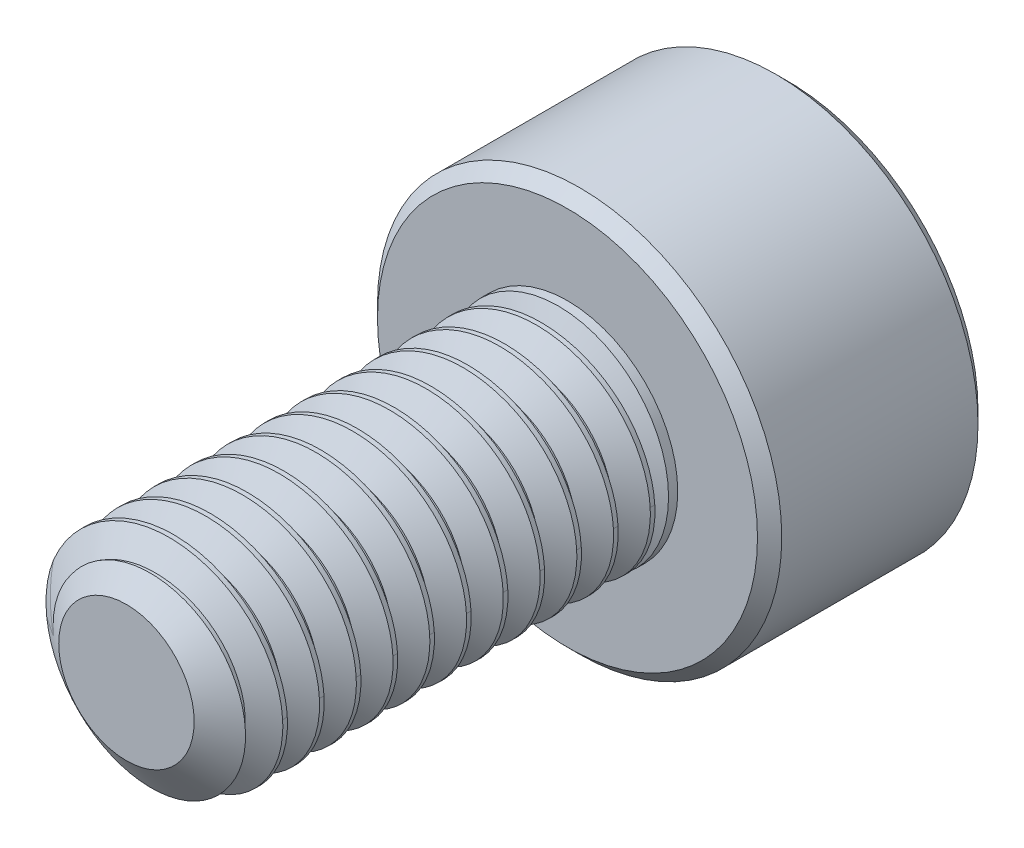
SolidWorks part; units mm, degrees
ref_plane "Front Plane" through (0, 0, 0) normal (0, 0, 1) x (1, 0, 0)
ref_plane "Top Plane" through (0, 0, 0) normal (0, 1, 0) x (1, 0, 0)
ref_plane "Right Plane" through (0, 0, 0) normal (1, 0, 0) x (0, 0, -1)
sketch "Sketch1" plane through (0, 0, 0) normal (0, 0, 1) x (1, 0, 0)
  circle A0 centre (0, 0) radius 1.5
  dimension "OD" = 3
extrude "Extrude1" add sketch "Sketch1" against normal blind 6
sketch "Sketch2" plane through (0, 0, 0) normal (0, 0, 1) x (1, 0, 0)
  circle A0 centre (0, 0) radius 1.5 construction
  circle A1 centre (0, 0) radius 1.5
curve "Helix/Spiral1" pitch 0.5 height 6.5 radius 1.5 centre (0, 0, 0) axis (0, 0, -1) start towards (0, 1, 0) parameters "pitch"=0.5
sketch "Sketch3" plane through (0, 0, 0) normal (1, 0, 0) x (0, 0, -1)
  line L0 (-0.4375, 1.5) -> (-0.25, 1.1752)
  line L1 (-0.25, 1.1752) -> (-0.1875, 1.1752)
  line L2 (-0.1875, 1.1752) -> (0, 1.5)
  line L3 (-0.4375, 1.5) -> (0, 1.5)
  line L4 (-0.2187, 1.5) -> (-0.2187, 1.1752) construction
  line L5 (-0.3437, 1.3376) -> (-0.0937, 1.3376) construction
  line L6 (0, 1.5) -> (0, -1.5) construction
  line L7 (0, -1.5) -> (6, -1.5) construction
  point P11 (2.25, -1.5)
  dimension "D1" = 0.0625
  dimension "D2" = 0.25
  dimension "D3" = 60
  dimension "D4" = 2.25
sweep "Cut-Sweep1" cut profiles "Sketch3" path "Helix/Spiral1" align with end faces yes
sketch "Sketch4" plane through (0, 0, 0) normal (1, 0, 0) x (0, 0, -1)
  line L0 (0.4053, 1.5) -> (0, 0.9212)
  line L1 (0, 0.9212) -> (0, 1.5)
  line L2 (0.4053, 1.5) -> (0, 1.5)
  line L3 (-0.4375, 1.5) -> (0, 1.5) construction
  line L4 (0, 0) -> (7.0209, 0) construction
  dimension "D1" = 55
  dimension "D2" = 0.254
revolve "Cut-Revolve1" cut sketch "Sketch4" angle 360 about L4
sketch "Sketch5" plane through (0, 0, 0) normal (1, 0, 0) x (0, 0, -1)
  line L0 (6, -1.1822) -> (6, 1.0703) construction
  line L1 (6, 1.5) -> (0.1203, 1.5)
  line L2 (6, 1.5) -> (6, 0)
  line L3 (6, 0) -> (0.0001, 0)
  line L4 (0.0001, 1.1698) -> (0.0001, 0)
  line L5 (0.1203, 1.5) -> (0.0001, 1.1698)
  line L6 (0, 0) -> (9.9695, 0) construction
  point P3 (0.0001, 1.5)
  point P10 (0.0001, 1.5)
  dimension "D1" = 0.3302
  dimension "Thread min" = 0.0001
  dimension "D3" = 20
revolve "partially thread" [suppressed] add sketch "Sketch5" angle 360 about L6
sketch "Sketch6" plane through (0, 0, -6) normal (0, 0, -1) x (-1, 0, 0)
  circle A0 centre (0, 0) radius 2.75
  dimension "head dia" = 5.5
extrude "Extrude2" add sketch "Sketch6" along normal blind 3
sketch "Sketch7" plane through (0, 0, -9) normal (0, 0, -1) x (-1, 0, 0)
  line L1 (0, 1.4434) -> (-1.25, 0.7217)
  line L2 (-1.25, 0.7217) -> (-1.25, -0.7217)
  line L3 (-1.25, -0.7217) -> (0, -1.4434)
  line L4 (0, -1.4434) -> (1.25, -0.7217)
  line L5 (1.25, -0.7217) -> (1.25, 0.7217)
  line L6 (1.25, 0.7217) -> (0, 1.4434)
  circle A0 centre (0, 0) radius 1.25 construction
  dimension "hex dia" = 2.5
extrude "Cut-Extrude1" cut sketch "Sketch7" against normal blind 1.875
sketch "Sketch8" plane through (0, 0, -9) normal (0, 0, -1) x (-1, 0, 0)
  circle A0 centre (0, 0) radius 1.4434
extrude "Cut-Extrude2" cut sketch "Sketch8" against normal through all draft 45
chamfer "Chamfer1" distance 0.165 angle 45 2 edges at (-2.75, 0, -9) (-2.75, 0, -6)
sketch "Sketch9" plane through (0, 0, 0) normal (1, 0, 0) x (0, 0, -1)
  line L0 (0, 1.5) -> (0, -1.5) construction
  line L1 (2.75, 1.5) -> (2.75, -1.5) construction
  dimension "D1" = 2.75
sketch "Sketch10" plane through (0, 0, 0) normal (1, 0, 0) x (0, 0, -1)
  line L0 (6, 1.5) -> (6, 0)
  line L1 (6, 1.5) -> (5.875, 1.5)
  line L2 (5.875, 1.5) -> (5.2537, 0)
  line L3 (6, 0) -> (5.2537, 0)
  line L4 (6, 2.585) -> (6, -2.585) construction
  dimension "D1" = 22.5
  dimension "D2" = 0.125
revolve "Revolve1" add sketch "Sketch10" angle 360 about L3
equation "\"D3@Helix/Spiral1\" = \"screw length@Extrude1\"+\"pitch@Helix/Spiral1\""
equation "\"D1@Sketch3\" = \"pitch@Helix/Spiral1\"*.125"
equation "\"D2@Sketch3\" = \"pitch@Helix/Spiral1\"*.5"
equation "\"D1@Cut-Extrude1\" = \"hex dia@Sketch7\"*.75"
equation "\"D1@Chamfer1\" = \"head dia@Sketch6\"*.03"
equation "\"D1@Sketch9\" = \"pitch@Helix/Spiral1\"*5.5"
equation "\"D2@Sketch10\" = \"pitch@Helix/Spiral1\"*.25"
equation "\"D4@Sketch3\" = \"pitch@Helix/Spiral1\"*4.50"
